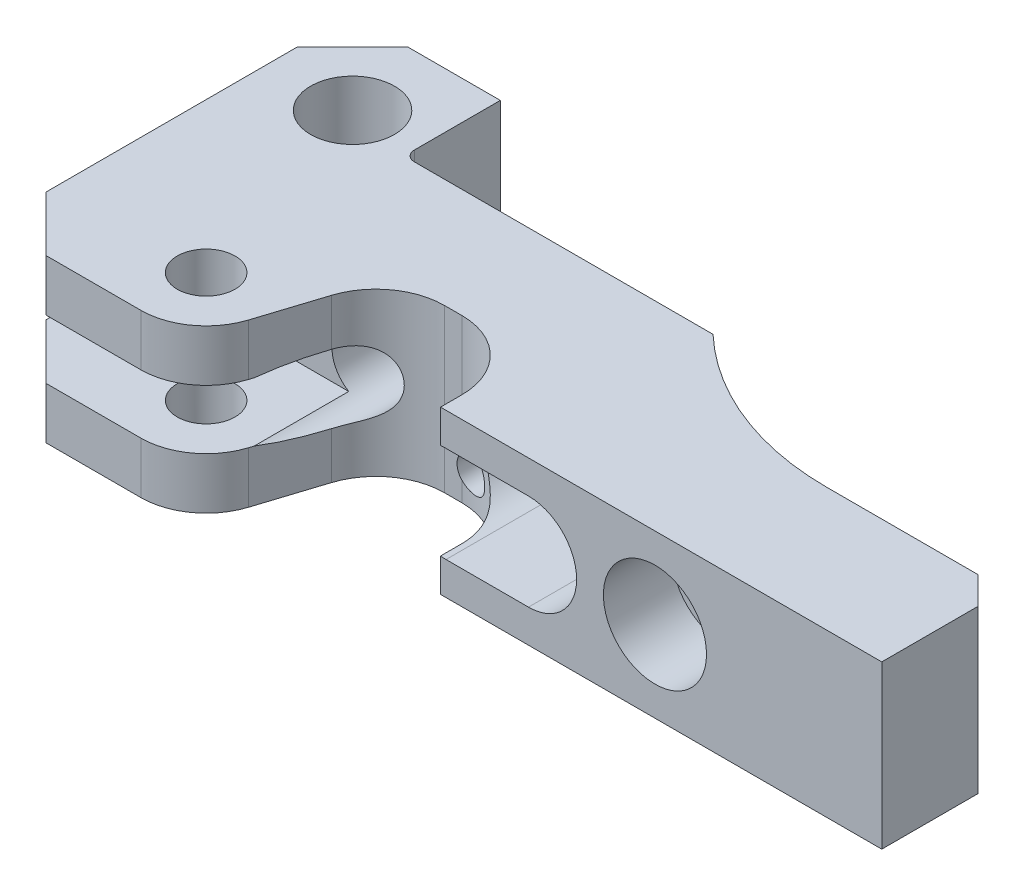
SolidWorks part; units mm, degrees
material "Al-2030 T4 (barra)"
ref_plane "Alzado" through (0, 0, 0) normal (0, 0, 1) x (1, 0, 0)
ref_plane "Planta" through (0, 0, 0) normal (0, 1, 0) x (1, 0, 0)
ref_plane "Vista lateral" through (0, 0, 0) normal (1, 0, 0) x (0, 0, -1)
sketch "Croquis1" plane through (0, 0, 0) normal (0, 1, 0) x (1, 0, 0)
  line L0 (16.9, -8.95) -> (15.65, -8.95)
  line L1 (-6, -20.3) -> (4.9, -20.3)
  line L2 (-6, 6) -> (54, 6)
  line L3 (4.9, -15.55) -> (4.9, -27.4514) construction
  line L4 (10.0265, -17.9071) -> (10.5529, -13.2869) construction
  line L5 (10.8882, -12.4252) -> (9.4237, -16.9986)
  line L7 (21.9, -13.95) -> (21.9, -15.5)
  line L11 (-6, 6) -> (-6, -20.3)
  line L12 (54, -15.5) -> (54, 6)
  line L16 (15.7, -8.5) -> (20.4167, -8.5) construction
  line L18 (21.9, -15.5) -> (54, -15.5)
  circle A0 centre (0, 0) radius 3.05
  circle A1 centre (4.9, -15.55) radius 1.5
  arc A2 (4.9, -20.3) -> (9.4237, -16.9986) centre (4.9, -15.55) ccw
  arc A3 (15.65, -8.95) -> (10.8882, -12.4252) centre (15.65, -13.95) ccw
  arc A4 (10.5529, -13.2869) -> (21.3107, -15.5) centre (16.0311, -13.9109) cw construction
  arc A8 (21.9, -13.95) -> (16.9, -8.95) centre (16.9, -13.95) ccw
  point P14 (4.65, -3)
  point P15 (37.8, -3)
  point P16 (1.75, 3.75)
  point P17 (54, 9.8827)
  dimension "D1" = 6.1
  dimension "D2" = 21.5
  dimension "D8" = 12
  dimension "D9" = 3
  dimension "D7" = 6
  dimension "D14" = 6
  dimension "D17" = 9.5
  dimension "D3" = 4.9
  dimension "D6" = 1.6
  dimension "D11" = 5
  dimension "D4" = 15.55
  dimension "D5" = 8.5
  dimension "D10" = 60
  dimension "D12" = 1.25
extrude "Saliente-Extruir1" add sketch "Croquis1" along normal blind 11.8 contours L12 A0 region at (23.7953, 0, 5.13)
sketch "Croquis26" [suppressed] plane through (0, 11.8, 0) normal (0, 1, 0) x (1, 0, 0)
  line L0 (9.4726, -17.0409) -> (10.669, -13.2109)
  line L1 (9.7, -15.55) -> (9.7, -9) construction
  line L2 (22.396, -15) -> (22.396, -17.55)
  line L3 (4.7, -15.55) -> (14.7, -15.55) construction
  line L4 (22.396, -17.55) -> (23.291, -17.55)
  line L5 (9.7, -9) -> (21, -9) construction
  line L6 (21, -9) -> (23.291, -17.55) construction
  line L7 (23.291, -17.55) -> (23.291, -8)
  line L8 (23.291, -8) -> (9.7, -8)
  line L9 (9.7, -8) -> (9.7, -9)
  line L10 (22.7, -17.55) -> (54, -17.55) construction
  line L28 (9.2833, -17.5483) -> (9.7, -9)
  arc A0 (9.4726, -17.0409) -> (9.2833, -17.5483) centre (4.7, -15.55) ccw
  arc A1 (22.1916, -13.4471) -> (22.396, -15) centre (16.396, -15) cw
  arc A4 (4.7, -20.55) -> (9.2833, -17.5483) centre (4.7, -15.55) ccw construction
  arc A5 (10.669, -13.2109) -> (22.1916, -13.4471) centre (16.396, -15) cw
  dimension "D2" = 1
  dimension "D4" = 6
extrude "Saliente-Extruir7" [suppressed] add sketch "Croquis26" against normal up to surface (11.8 mm away)
hole_wizard "Taladro roscado M51" positions "Croquis11" profile "Croquis10" tap size "M5" standard "ISO" end condition through all
sketch "Croquis11" plane through (0, 11.8, 0) normal (0, 1, 0) x (1, 0, 0)
  circle A0 centre (4.9, -15.55) radius 1.5 construction
  point P0 (4.9, -15.55)
cosmetic thread "Rosca de taladro1" parameters "D2"=5
sketch "Croquis10" plane through (4.9, 11.8, 15.55) normal (1, 0, 0) x (0, 0, 1)
  line L0 (0, 0) -> (0, 11.8)
  line L1 (0, 11.8) -> (2.1, 11.8)
  line L2 (2.1, 11.8) -> (2.1, 0)
  line L5 (2.1, 0) -> (0, 0)
  line L11 (0, -6.35) -> (0, 107.95) construction
  dimension "Diámetro de perforador para roscar hasta el siguiente" = 4.2
  dimension "Profundidad de perforador para roscar hasta el siguiente" = 11.8
sketch "Croquis2" plane through (-6, 0, 0) normal (-1, 0, 0) x (0, 0, 1)
  line L0 (20.3, 5.9) -> (-6, 5.9) construction
  line L1 (20.3, 11.8) -> (20.3, 0) construction
  line L2 (17.65, 11.8) -> (13.45, 11.8) construction
  line L3 (-6, 11.8) -> (-6, 0) construction
  line L4 (9.8, 3.75) -> (20.3, 3.75)
  line L5 (9.8, 3.75) -> (9.8, 8.05)
  line L6 (9.8, 8.05) -> (20.3, 8.05)
  line L7 (20.3, 3.75) -> (20.3, 8.05)
  line L8 (15.55, 11.8) -> (15.55, 0) construction
  line L9 (13.45, 0) -> (17.65, 0) construction
  dimension "D1" = 11.5
  dimension "D2" = 4.3
extrude "Cortar-Extruir1" cut sketch "Croquis2" against normal blind 18
sketch "Croquis13" plane through (0, 0, 9.8) normal (0, 0, 1) x (1, 0, 0)
  line L0 (-6, 8.05) -> (-6, 3.75) construction
  line L1 (-6, 5.9) -> (10.8, 5.9) construction
  line L3 (0, 11.8) -> (0, -15.0383) construction
  line L4 (3.05, 11.8) -> (-3.05, 11.8) construction
  circle A0 centre (10.8, 5.9) radius 2.5
  dimension "D2" = 5
  dimension "D1" = 10.8
extrude "Cortar-Extruir6" cut sketch "Croquis13" against normal through all and the other way through all
sketch "Croquis27" plane through (0, 0, -6) normal (0, 0, -1) x (-1, 0, 0)
  circle A0 centre (-10.8, 5.9) radius 3.1
  dimension "D1" = 6.2
extrude "Cortar-Extruir8" cut sketch "Croquis27" against normal blind 10
sketch "Croquis31" plane through (0, 0, 15.5) normal (0, 0, 1) x (1, 0, 0)
  line L0 (-6, 5.9) -> (37.5, 5.9) construction
  line L1 (0, 0) -> (0, 25.0198) construction
  line L2 (-3.05, 0) -> (3.05, 0) construction
  line L3 (-6, 11.8) -> (-6, 0) construction
  circle A0 centre (37.5, 5.9) radius 3.75
  dimension "D2" = 7.5
  dimension "D1" = 37.5
extrude "Cortar-Extruir9" cut sketch "Croquis31" against normal blind 5
sketch "Croquis32" plane through (0, 0, 15.5) normal (0, 0, 1) x (1, 0, 0)
  line L0 (37.5, 5.9) -> (26, 5.9) construction
  line L1 (0, 11.8) -> (0, -11.2724) construction
  line L2 (3.05, 11.8) -> (-3.05, 11.8) construction
  circle A0 centre (26, 5.9) radius 4
  dimension "D2" = 8
  dimension "D1" = 26
extrude "Cortar-Extruir10" [suppressed] cut sketch "Croquis32" against normal blind 5
sketch "Croquis33" [suppressed] plane through (0, 0, 0) normal (0, -1, 0) x (1, 0, 0)
  line L0 (22.3, 17.55) -> (54, 17.55) construction
  line L1 (32.5, 17.55) -> (18.9852, 17.55)
  line L2 (32.5, 17.55) -> (32.5, 16.55) construction
  line L3 (32.5, 16.55) -> (18.9852, 16.55)
  line L4 (18.9852, 17.55) -> (18.9852, 16.55)
  line L5 (32.5, 16.55) -> (62.9265, 16.55)
  line L6 (62.9265, 16.55) -> (62.9265, 17.55)
  line L7 (62.9265, 17.55) -> (32.5, 17.55)
  dimension "D1" = 32.5
  dimension "D2" = 1
extrude "Cortar-Extruir11" [suppressed] cut sketch "Croquis33" against normal through all
sketch "Croquis34" plane through (0, 0, 0) normal (0, -1, 0) x (1, 0, 0)
  line L0 (54, 15.5) -> (54, -6) construction
  line L2 (-6, -6) -> (54, -6) construction
  line L4 (54, 6.5) -> (41, 6.5)
  line L7 (-6, -6) -> (-6, 20.3) construction
  line L8 (22.4595, -6) -> (54, -6)
  line L9 (54, -6) -> (54, 6.5)
  arc A0 (41, 6.5) -> (22.4595, -6) centre (41, -13.5) ccw
  dimension "D2" = 20
  dimension "D1" = 12.5
  dimension "D4" = 47
extrude "Cortar-Extruir12" cut sketch "Croquis34" against normal through all
chamfer "Chaflán2" distance 4 angle 45 1 edges at (-6, 5.9, -6)
ref_plane "Plano1" [suppressed] through (0, 5.9, 0) normal (0, 1, 0) x (1, 0, 0)
chamfer "Chaflán3" distance 2 angle 45 1 edges at (54, 5.9, 6.5)
ref_plane "Plano2" through (0, 5.9, 0) normal (0, -1, 0) x (-1, 0, 0)
sketch "Croquis35" plane through (0, 5.9, 0) normal (0, -1, 0) x (-1, 0, 0)
  line L0 (-13.9, -4) -> (-10.8, -9.3694)
  line L1 (-7.7, -4) -> (-13.9, -4) construction
  line L2 (-10.8, -9.3694) -> (-10.8, -4)
  line L3 (-10.8, -4) -> (-13.9, -4)
  line L4 (-8.3, -4) -> (-13.3, -4) construction
  line L5 (-10.8, -4) -> (-10.8, 1.8195) construction
  dimension "D1" = 60
revolve "Cortar-Revolución1" cut sketch "Croquis35" angle 360 about L5
sketch "Croquis36" plane through (0, 0, -6) normal (0, 0, -1) x (-1, 0, 0)
  line L0 (-18.3, 5.9) -> (-10.8, 5.9) construction
  circle A0 centre (-18.3, 5.9) radius 3
  circle A1 centre (-10.8, 5.9) radius 3.1 construction
  dimension "D2" = 6
  dimension "D1" = 7.5
extrude "Cortar-Extruir13" [suppressed] cut sketch "Croquis36" against normal through all
sketch "Croquis37" [suppressed] plane through (0, 3.85, 0) normal (0, 1, 0) x (1, 0, 0)
  line L1 (9.6826, -17.0083) -> (10.6609, -13.8) construction
  line L2 (9.6826, -17.0083) -> (10.6609, -13.8)
  line L4 (9.3691, -17.7921) -> (9.3691, -9.8)
  line L5 (9.3691, -9.8) -> (-6, -9.8)
  line L6 (-6, -9.8) -> (-6, -20.55)
  line L7 (-6, -20.55) -> (4.9, -20.55)
  line L9 (14.6861, -9.8) -> (-6, -9.8)
  line L10 (-6, -9.8) -> (-6, -20.55)
  line L11 (-6, -20.55) -> (4.9, -20.55)
  arc A0 (22.4, -15.55) -> (10.6609, -13.8) centre (16.4, -15.55) ccw construction
  arc A1 (4.9, -20.55) -> (9.3691, -17.7921) centre (4.9, -15.55) ccw
  arc A2 (4.9, -20.55) -> (9.6826, -17.0083) centre (4.9, -15.55) ccw
  arc A3 (14.6861, -9.8) -> (10.6609, -13.8) centre (16.4, -15.55) ccw
  dimension "D1" = 0
extrude "Cortar-Extruir14" [suppressed] cut sketch "Croquis37" against normal up to next
sketch "Croquis38" [suppressed] plane through (0, 7.95, 0) normal (0, -1, 0) x (1, 0, 0)
  circle A0 centre (4.9, 15.55) radius 5
  circle A1 centre (4.9, 15.55) radius 1.5
  dimension "D1" = 10
  dimension "D2" = 3
extrude "Saliente-Extruir8" [suppressed] add sketch "Croquis38" along normal blind 4 from offset 0.5 separate body
sketch "Croquis39" [suppressed] plane through (0, 3.45, 0) normal (0, -1, 0) x (1, 0, 0)
  circle A0 centre (4.9, 15.55) radius 5 construction
  circle A1 centre (4.9, 15.55) radius 5
  circle A2 centre (4.9, 15.55) radius 5.75
  dimension "D1" = 0.75
extrude "Saliente-Extruir9" [suppressed] add sketch "Croquis39" against normal blind 1 separate body
sketch "Croquis41" [suppressed] plane through (0, 3.45, 0) normal (0, -1, 0) x (1, 0, 0)
  circle A0 centre (4.9, 15.55) radius 2.75
  dimension "D1" = 5.5
extrude "Saliente-Extruir11" [suppressed] add sketch "Croquis41" along normal blind 2.5 separate body
sketch "Croquis42" [suppressed] plane through (0, 0.95, 0) normal (0, -1, 0) x (1, 0, 0)
  line L1 (4.9, 16.9934) -> (3.65, 16.2717)
  line L2 (3.65, 16.2717) -> (3.65, 14.8283)
  line L3 (3.65, 14.8283) -> (4.9, 14.1066)
  line L4 (4.9, 14.1066) -> (6.15, 14.8283)
  line L5 (6.15, 14.8283) -> (6.15, 16.2717)
  line L6 (6.15, 16.2717) -> (4.9, 16.9934)
  circle A0 centre (4.9, 15.55) radius 1.25 construction
  dimension "D1" = 2.5
extrude "Cortar-Extruir15" [suppressed] cut sketch "Croquis42" against normal blind 1.5
fillet "Redondeo1" [suppressed] radius 0.5
sketch "Croquis43" [suppressed] plane through (0, 3.45, 0) normal (0, -1, 0) x (1, 0, 0)
  circle A0 centre (4.9, 15.55) radius 3.25
  circle A1 centre (4.9, 15.55) radius 5.75
  circle A2 centre (4.9, 15.55) radius 5.75 construction
  dimension "D1" = 6.5
extrude "Saliente-Extruir12" [suppressed] add sketch "Croquis43" along normal blind 0.8 separate body
sketch "Croquis44" [suppressed] plane through (0, 2.65, 0) normal (0, -1, 0) x (1, 0, 0)
  line L0 (4.9, 12.3) -> (4.9, 9.8)
  line L1 (4.9, 12.3) -> (4.9, 15.55) construction
  line L2 (3.6563, 12.5474) -> (2.6996, 10.2377)
  line L3 (2.6019, 13.2519) -> (0.8341, 11.4841)
  line L4 (1.8974, 14.3063) -> (-0.4123, 13.3496)
  line L5 (1.65, 15.55) -> (-0.85, 15.55)
  line L6 (1.8974, 16.7937) -> (-0.4123, 17.7504)
  line L7 (2.6019, 17.8481) -> (0.8341, 19.6159)
  line L8 (3.6563, 18.5526) -> (2.6996, 20.8623)
  line L9 (4.9, 18.8) -> (4.9, 21.3)
  line L10 (6.1437, 18.5526) -> (7.1004, 20.8623)
  line L11 (7.1981, 17.8481) -> (8.9659, 19.6159)
  line L12 (7.9026, 16.7937) -> (10.2123, 17.7504)
  line L13 (8.15, 15.55) -> (10.65, 15.55)
  line L14 (7.9026, 14.3063) -> (10.2123, 13.3496)
  line L15 (7.1981, 13.2519) -> (8.9659, 11.4841)
  line L16 (6.1437, 12.5474) -> (7.1004, 10.2377)
  line L17 (4.9, 15.55) -> (4.9, 12.3) construction
  line L18 (4.9, 15.55) -> (3.6563, 12.5474) construction
  circle A0 centre (4.9, 15.55) radius 3.25 construction
  circle A1 centre (4.9, 15.55) radius 5.75 construction
  circle A2 centre (4.9, 15.55) radius 5.75
  circle A3 centre (4.9, 15.55) radius 3.25
  circle M17 centre (4.9, 15.55) radius 5.75
  circle M18 centre (4.9, 15.55) radius 3.25
  dimension "D1" = 16
  dimension "D2" = 22.5
extrude "Cortar-Extruir16" [suppressed] cut sketch "Croquis44" against normal blind 0.05 contours L16 L0 M18 M17 | L3 L2 M18 M17 | L5 L4 M18 M17 | L7 L6 M18 M17 | L9 L8 M18 M17 | L11 L10 M18 M17 | L13 L12 M18 M17 | L15 L14 M18 M17
chamfer "Chaflán4" [suppressed] distance 12 angle 7
sketch "Croquis45" plane through (0, 0, -6) normal (0, 0, -1) x (-1, 0, 0)
  line L0 (-22.3, 5.9) -> (-28.3, 5.9) construction
  line L1 (-22.3, 2.4) -> (-28.3, 2.4)
  line L2 (-22.3, 9.4) -> (-28.3, 9.4)
  line L3 (-21.3, 5.9) -> (-22.3, 5.9) construction
  line L4 (-10.8, 5.9) -> (-21.3, 5.9) construction
  arc A0 (-22.3, 2.4) -> (-22.3, 9.4) centre (-22.3, 5.9) ccw
  arc A1 (-28.3, 9.4) -> (-28.3, 2.4) centre (-28.3, 5.9) ccw
  point P3 (-25.3, 5.9)
  dimension "D4" = 10.5
  dimension "D1" = 7
  dimension "D2" = 1
  dimension "D3" = 6
extrude "Cortar-Extruir17" cut sketch "Croquis45" against normal through all
sketch "Croquis46" plane through (0, 0, 0) normal (0, -1, 0) x (1, 0, 0)
  line L0 (-2, -6) -> (22.4595, -6) construction
  line L1 (4.75, -6) -> (32.7996, -6)
  line L2 (4.75, -6) -> (4.75, 1)
  line L3 (4.75, 1) -> (32.7996, 1)
  line L4 (32.7996, -6) -> (32.7996, 1)
  dimension "D1" = 4.75
  dimension "D2" = 7
extrude "Cortar-Extruir18" cut sketch "Croquis46" against normal through all
hole_wizard "Taladro roscado M31" positions "Croquis48" profile "Croquis47" tap size "M3" standard "Iso"
sketch "Croquis48" plane through (0, 0, 1) normal (0, 0, -1) x (-1, 0, 0)
  circle A0 centre (-10.8, 5.9) radius 3.1 construction
  point P0 (-17.8, 2.3)
  dimension "D1" = 7
  dimension "D2" = 3.6
sketch "Croquis47" plane through (17.8, 2.3, 1) normal (1, 0, 0) x (0, 1, 0)
  line L0 (0, 0) -> (0, 8.5)
  line L1 (0, 8.5) -> (1.25, 8.5)
  line L2 (1.25, 8.5) -> (1.25, 0)
  line L5 (1.25, 0) -> (0, 0)
  line L10 (0, 8.5) -> (-1.25, 8.5) construction
  line L11 (0, -6.35) -> (0, 107.95) construction
  dimension "Diámetro de perforador para roscar" = 2.5
  dimension "Profundidad de perforador para roscar" = 8.5
  dimension "Ángulo de perforador" = 180
cosmetic thread "Rosca de taladro3" parameters "D1"=6, "D2"=3
fillet "Redondeo2" radius 0.75 1 edges at (4.75, 5.9, 1)
chamfer "Chaflán5" distance 0.6 angle 60 1 edges at (13.9, 5.9, 1) first distance on face at (16.55, 2.3, 1)
chamfer "Chaflán6" distance 4 angle 45 2 edges at (-6, 9.925, 20.3) (-6, 1.875, 20.3)
